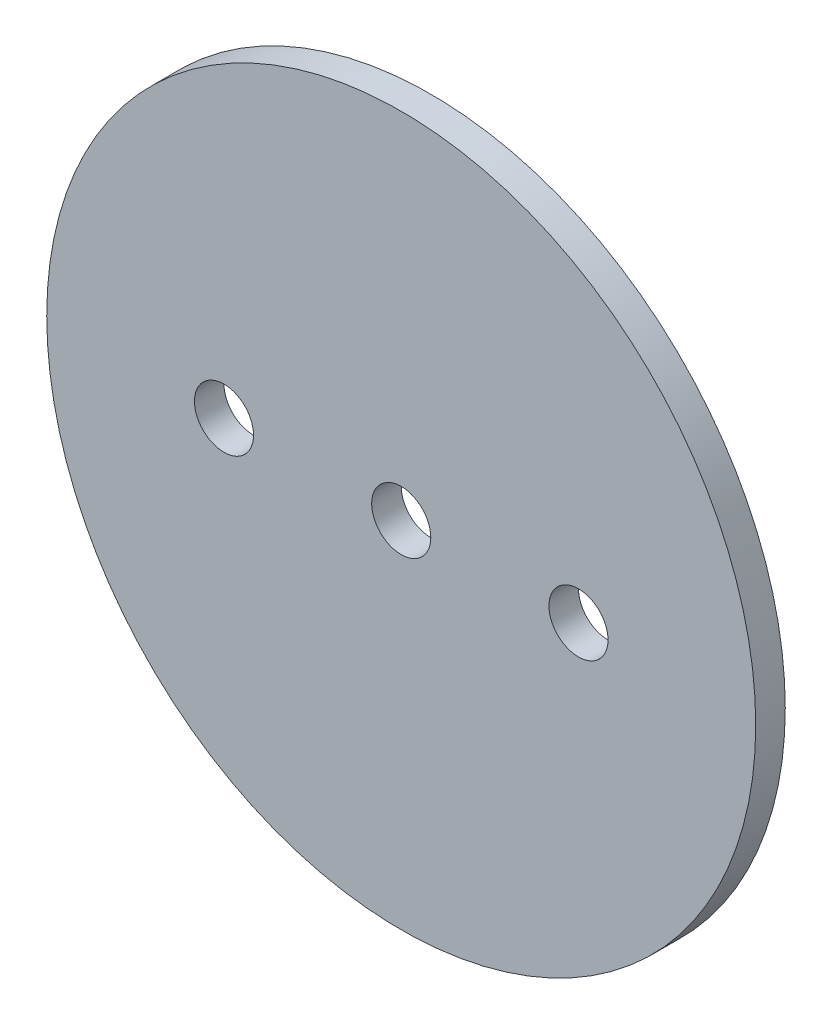
SolidWorks part; units mm, degrees
ref_plane "Front Plane" through (0, 0, 0) normal (0, 0, 1) x (1, 0, 0)
ref_plane "Top Plane" through (0, 0, 0) normal (0, 1, 0) x (1, 0, 0)
ref_plane "Right Plane" through (0, 0, 0) normal (1, 0, 0) x (0, 0, -1)
sketch "Sketch1" plane through (0, 0, 0) normal (0, 0, 1) x (1, 0, 0)
  circle A0 centre (0, 0) radius 38.1
extrude "Boss-Extrude1" add sketch "Sketch1" along normal mid plane 3.175
sketch "Sketch2" plane through (0, 0, 1.5875) normal (0, 0, 1) x (1, 0, 0)
  line L0 (-1000, 0) -> (49000, 0) construction
  point P1 (0, 0)
  point P4 (19.05, 0)
  point P5 (-19.05, 0)
  dimension "D1" = 19.05
  dimension "D2" = 38.1
hole_wizard "1/4 (0.25) Diameter Hole1" positions "Sketch2" profile "Sketch3" hole size "1/4" standard "ANSI Inch" end condition through all
sketch "Sketch3" plane through (-19.05, 0, 1.5875) normal (1, 0, 0) x (0, -1, 0)
  line L0 (0, 0) -> (0, 3.175)
  line L1 (0, 3.175) -> (3.175, 3.175)
  line L2 (3.175, 3.175) -> (3.175, 0)
  line L5 (3.175, 0) -> (0, 0)
  line L11 (0, -6.35) -> (0, 107.95) construction
  dimension "Thru Hole Dia." = 6.35
  dimension "Thru Hole Depth" = 3.175
equation "\"AIRFRAME_OD\"= 3.091in"
equation "\"AIRFRAME_ID\"= 3.00in"
equation "\"FLAT_T\"= 0.125in"
equation "\"NOSE_EXP_L\"= 3.5in"
equation "\"NOSE_SHOULDER_L\"= 5in"
equation "\"MAIN_L\"= 30in"
equation "\"RECO_COUP_L\"= 6in"
equation "\"RECO_SWITCH_L\"= 1.5in"
equation "\"DROGUE_L\"= 14in"
equation "\"ATS_FORE_COUP_L\"= 4in"
equation "\"ATS_AFT_COUP_L\"= 4in"
equation "\"LOWER_L\"= 16in"
equation "\"FIN_N\"= 4"
equation "\"CR_AFT_X\"= 0.5in"
equation "\"CR_FORE_X\"= 6in"
equation "\"FIN_ROOT\"= 5in"
equation "\"FIN_X\"= 0.75in"
equation "\"MOTOR_OD\"= 2.25in"
equation "\"MOTOR_ID\"= 2.126in"
equation "\"COUPLER_OD\"= 2.998in"
equation "\"COUPLER_ID\"= 2.875in"
equation "\"D1@Sketch1\"=\"AIRFRAME_ID\""
equation "\"D1@Boss-Extrude1\"=\"FLAT_T\""
equation "\"RECO_ROD_X\"= 1.5in"
equation "\"ATS_ROD_X\"= 2in"
equation "\"D1@Sketch2\"=\"RECO_ROD_X\"*0.5"
equation "\"D2@Sketch2\"=\"RECO_ROD_X\""
